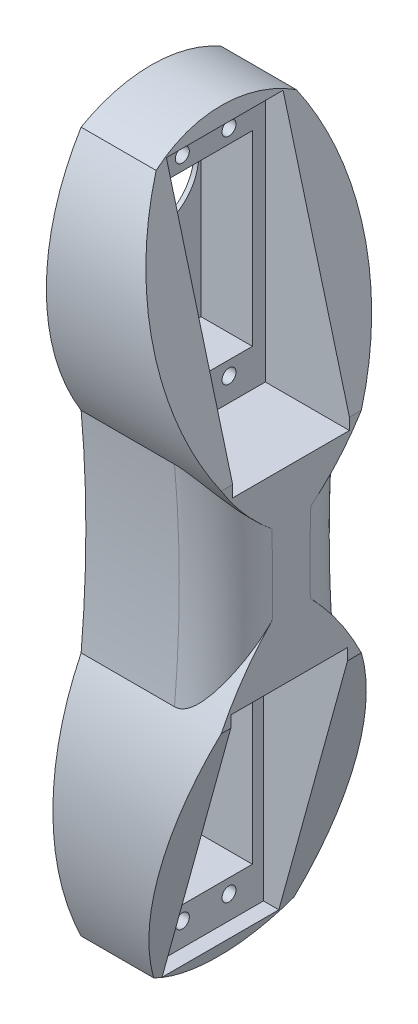
SolidWorks part; units mm, degrees
ref_plane "Front Plane" through (0, 0, 0) normal (0, 0, 1) x (1, 0, 0)
ref_plane "Top Plane" through (0, 0, 0) normal (0, 1, 0) x (1, 0, 0)
ref_plane "Right Plane" through (0, 0, 0) normal (1, 0, 0) x (0, 0, -1)
sketch "Sketch1" plane through (0, 0, 0) normal (1, 0, 0) x (0, 0, -1)
  line L9 (-15, 75) -> (15, -75) construction
  line L10 (-15, -75) -> (15, 75) construction
  line L19 (-15, 22.4886) -> (15, -22.4886) construction
  line L20 (-15, -22.4886) -> (15, 22.4886) construction
  arc A2 (15, 22.4886) -> (15, -22.4886) centre (263.9865, 0) ccw
  arc A3 (-15, 22.4886) -> (-15, -22.4886) centre (-263.9865, 0) cw
  arc A4 (-15, 75) -> (15, 75) centre (0, 49.0192) cw
  arc A5 (-15, -75) -> (15, -75) centre (0, -49.0192) ccw
  arc A6 (15, 75) -> (15, 22.4886) centre (-27.5516, 48.7443) cw
  arc A7 (-15, 75) -> (-15, 22.4886) centre (27.5516, 48.7443) ccw
  arc A8 (15, -22.4886) -> (15, -75) centre (-38.9503, -48.7443) cw
  arc A9 (-15, -22.4886) -> (-15, -75) centre (38.9503, -48.7443) ccw
  point P0 (0, 0)
  point P9 (0, 0)
  dimension "D3" = 250
  dimension "D4" = 30
  dimension "D5" = 250
  dimension "D6" = 50
  dimension "D7" = 50
  dimension "D8" = 60
  dimension "D1" = 150
  dimension "D2" = 30
extrude "Boss-Extrude1" add sketch "Sketch1" along normal blind 30
ref_plane "Plane1" through (30, 0, 0) normal (1, 0, 0) x (0, 0, -1)
sketch "Sketch2" plane through (30, 0, 0) normal (1, 0, 0) x (0, 0, -1)
  line L1 (-10.3316, 68.0192) -> (9.6684, 68.0192)
  line L2 (-10.3316, 68.0192) -> (-10.3316, 28.0192)
  line L3 (-10.3316, 28.0192) -> (9.6684, 28.0192)
  line L4 (9.6684, 68.0192) -> (9.6684, 28.0192)
  line L5 (-10.3316, 68.0192) -> (9.6684, 28.0192) construction
  line L6 (-10.3316, 28.0192) -> (9.6684, 68.0192) construction
  line L7 (-10.3316, -28.0192) -> (9.6684, -28.0192)
  line L8 (-10.3316, -28.0192) -> (-10.3316, -68.0192)
  line L9 (-10.3316, -68.0192) -> (9.6684, -68.0192)
  line L10 (9.6684, -28.0192) -> (9.6684, -68.0192)
  line L11 (-10.3316, -28.0192) -> (9.6684, -68.0192) construction
  line L12 (-10.3316, -68.0192) -> (9.6684, -28.0192) construction
  arc A0 (-15, -75) -> (15, -75) centre (0, -49.0192) ccw construction
  arc A1 (15, 75) -> (-15, 75) centre (0, 49.0192) ccw construction
  circle A2 centre (4.6684, 71.0192) radius 1.5
  circle A3 centre (-5.3316, 71.0192) radius 1.5
  circle A5 centre (4.6684, 25.0192) radius 1.5
  circle A6 centre (-5.3316, 24.8697) radius 1.5
  circle A7 centre (4.6684, -25.0192) radius 1.5
  circle A8 centre (-5.3316, -25.0192) radius 1.5
  circle A9 centre (4.6684, -71.0192) radius 1.5
  circle A10 centre (-5.3316, -71.0192) radius 1.5
  point P0 (-0.3316, 48.0192)
  point P5 (-0.3316, -48.0192)
  dimension "D5" = 19
  dimension "D7" = 3
  dimension "D8" = 3
  dimension "D9" = 10
  dimension "D10" = 5
  dimension "D11" = 3
  dimension "D12" = 3
  dimension "D13" = 3
  dimension "D14" = 3
  dimension "D15" = 3
  dimension "D16" = 3
  dimension "D17" = 3
  dimension "D18" = 10
  dimension "D19" = 3
  dimension "D20" = 3
  dimension "D21" = 10
  dimension "D22" = 3
  dimension "D1" = 40
  dimension "D2" = 20
  dimension "D3" = 40
  dimension "D4" = 20
  dimension "D6" = 19
extrude "Cut-Extrude1" cut sketch "Sketch2" against normal blind 29
sketch "Sketch3" plane through (30, 0, 0) normal (1, 0, 0) x (0, 0, -1)
  line L1 (-12.5516, 76.0192) -> (12.4484, 76.0192)
  line L2 (-12.5516, 76.0192) -> (-12.5516, 20.0192)
  line L3 (-12.5516, 20.0192) -> (12.4484, 20.0192)
  line L4 (12.4484, 76.0192) -> (12.4484, 20.0192)
  line L5 (-12.5516, 76.0192) -> (12.4484, 20.0192) construction
  line L6 (-12.5516, 20.0192) -> (12.4484, 76.0192) construction
  line L7 (-12.9503, -20.0192) -> (12.0497, -20.0192)
  line L8 (-12.9503, -20.0192) -> (-12.9503, -76.0192)
  line L9 (-12.9503, -76.0192) -> (12.0497, -76.0192)
  line L10 (12.0497, -20.0192) -> (12.0497, -76.0192)
  line L11 (-12.9503, -20.0192) -> (12.0497, -76.0192) construction
  line L12 (-12.9503, -76.0192) -> (12.0497, -20.0192) construction
  arc A1 (15, 75) -> (-15, 75) centre (0, 49.0192) ccw construction
  arc A3 (-15, -75) -> (15, -75) centre (0, -49.0192) ccw construction
  arc A4 (15, -75) -> (15, -22.4886) centre (-38.9503, -48.7443) ccw construction
  arc A5 (15, 22.4886) -> (15, 75) centre (-27.5516, 48.7443) ccw construction
  point P0 (-0.0516, 48.0192)
  point P8 (0, 79.0192)
  point P9 (-0.4503, -48.0192)
  dimension "D2" = 25
  dimension "D5" = 27
  dimension "D1" = 56
  dimension "D3" = 3
  dimension "D4" = 25
  dimension "53" = 56
  dimension "D6" = 40
  dimension "50" = 51
extrude "Cut-Extrude2" cut sketch "Sketch3" against normal blind 18
sketch "Sketch4" plane through (0, 0, 0) normal (0, 0, 1) x (1, 0, 0)
  line L0 (15, 79.0192) -> (30, 22.4886)
  line L1 (30, 79.0192) -> (0, 79.0192) construction
  line L2 (30, 22.4886) -> (30, -22.4886)
  line L3 (30, -22.4886) -> (14.2796, -79.6815)
  line L4 (14.2796, -79.6815) -> (43.0974, -79.6815)
  line L5 (43.0974, -79.6815) -> (43.0974, 80.45)
  line L6 (43.0974, 80.45) -> (15, 79.0192)
extrude "Cut-Extrude3" cut sketch "Sketch4" against normal blind 40 and the other way blind 40
sketch "Sketch5" plane through (0, 0, 0) normal (1, 0, 0) x (0, 0, -1)
  line L0 (9.6684, 68.0192) -> (-10.3316, 68.0192) construction
  line L1 (-10.3316, -68.0192) -> (9.6684, -68.0192) construction
  line L2 (-10.3316, -87.9748) -> (-10.3316, -68.0192) construction
  line L3 (-10.3316, 68.0192) -> (-10.3316, 90.3254) construction
  circle A0 centre (-0.3316, 58.0192) radius 9.5
  circle A1 centre (-0.3316, -58.0192) radius 9.5
  dimension "D1" = 19
  dimension "D2" = 10
  dimension "D3" = 19
  dimension "D4" = 10
  dimension "D5" = 10
  dimension "D6" = 10
extrude "Cut-Extrude4" cut sketch "Sketch5" along normal blind 40
fillet "Fillet1" radius 10 1 edges at (30, 0, -13.9865)
fillet "Fillet2" radius 10 1 edges at (30, 0, 13.9865)
